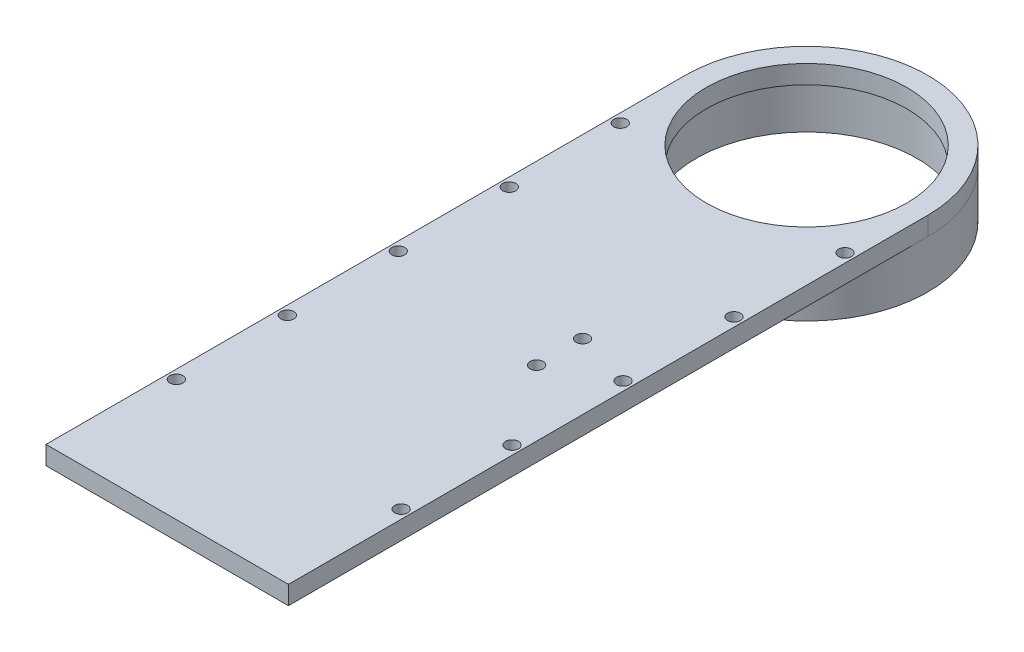
SolidWorks part; units mm, degrees
ref_plane "Front Plane" through (0, 0, 0) normal (0, 0, 1) x (1, 0, 0)
ref_plane "Top Plane" through (0, 0, 0) normal (0, 1, 0) x (1, 0, 0)
ref_plane "Right Plane" through (0, 0, 0) normal (1, 0, 0) x (0, 0, -1)
sketch "Sketch1" plane through (0, 0, 0) normal (0, 1, 0) x (1, 0, 0)
  line L5 (-32.774, -22.3805) -> (-32.774, 177.6195)
  line L6 (32.774, -22.3805) -> (32.774, 177.6195)
  circle A3 centre (0, 177.6195) radius 4.5
  circle A4 centre (0, 67.6378) radius 4.5
  circle A5 centre (15, 89.6378) radius 1.75
  circle A7 centre (-6.7334, 37.1195) radius 1.25
  circle A8 centre (-6.7334, 27.6195) radius 1.25
  circle A14 centre (0, 53.6052) radius 1.75
  circle A15 centre (-14.0327, 67.6378) radius 1.75
  circle A16 centre (0, 81.6705) radius 1.75
  circle A17 centre (14.0327, 67.6378) radius 1.75
  circle A18 centre (0, 67.6378) radius 11.5
  circle A19 centre (0, 67.6378) radius 4.5
  arc A22 (32.774, -22.3805) -> (-32.774, -22.3805) centre (0, -22.3805) cw
  arc A23 (32.774, 177.6195) -> (-32.774, 177.6195) centre (0, 177.6195) ccw
  circle A25 centre (0, -9.3805) radius 2.75
  circle A27 centre (11.2583, -15.8805) radius 2.75
  circle A28 centre (11.2583, -28.8805) radius 2.75
  circle A29 centre (0, -35.3805) radius 2.75
  circle A30 centre (-11.2583, -28.8805) radius 2.75
  circle A31 centre (-11.2583, -15.8805) radius 2.75
  dimension "D1" = 13
  dimension "D2" = 200
  dimension "D3" = 50
  dimension "D4" = 109.9817
  dimension "D5" = 22
  dimension "D8" = 9.5
  dimension "D6" = 15
extrude "Boss-Extrude10" add sketch "Sketch1" against normal blind 5 contours L6 A23 L5 A22 A31 A30 A29 A28 A27 A25 A3 A5 A7 A8 A14 A15 A16 A17 A18 | A18 | A19 region at (-30.0388, 0, -77.6195)
sketch "Sketch2" plane through (0, 0, 0) normal (0, -1, 0) x (1, 0, 0)
  line L30 (28, -177.6198) -> (28, -97.6193)
  line L31 (-28, -4.769) -> (-32.774, -4.769)
  line L35 (-28, -177.6198) -> (-28, -97.62)
  line L46 (-28, -4.769) -> (28, -4.769)
  line L53 (28, -4.769) -> (32.774, -4.769)
  line L54 (-32.774, 22.3805) -> (-32.774, -177.6198)
  line L55 (32.774, 22.3805) -> (32.774, -177.6198)
  line L56 (-28, 22.3805) -> (-28, -97.62)
  line L57 (28, -97.6193) -> (28, 22.3805)
  circle A4 centre (-18, -157.4003) radius 1.75
  circle A5 centre (18.0605, -157.4003) radius 1.75
  circle A6 centre (-18, -97.6199) radius 1.75
  circle A7 centre (18.0032, -97.4003) radius 1.75
  arc A15 (28, -177.6198) -> (-28, -177.6198) centre (0, -177.6198) cw
  arc A26 (32.774, 22.3805) -> (-32.774, 22.3805) centre (0, 22.3805) ccw
  arc A28 (-32.774, -177.6198) -> (32.774, -177.6198) centre (0, -177.6198) ccw
  arc A29 (28, 22.3805) -> (-28, 22.3805) centre (0, 22.3805) ccw
  dimension "D1" = 60
extrude "Boss-Extrude11" add sketch "Sketch1<16>" against normal blind 5 contours A7 | A8 region at (-6.7334, 0, -37.1195) region at (-6.7334, 0, -27.6195)
sketch "Sketch1<16>" plane through (0, 0, 0) normal (0, 1, 0) x (1, 0, 0) same geometry as "Sketch1"
sketch "Sketch3" plane through (0, -5, 0) normal (0, -1, 0) x (1, 0, 0)
  line L2 (-32.774, 22.3805) -> (-32.774, -177.6195) construction
  circle A0 centre (15, -89.6378) radius 1.75
  circle A4 centre (15, -102.0563) radius 1.75
  circle A6 centre (-30.384, -67.6195) radius 1.75
  circle A7 centre (-30.384, -37.6195) radius 1.75
  arc A8 (32.774, 22.3805) -> (-32.774, 22.3805) centre (0, 22.3805) ccw construction
  circle A9 centre (-30.384, -97.6195) radius 1.75
  circle A10 centre (-30.384, -127.6195) radius 1.75
  circle A11 centre (-30.384, -157.6195) radius 1.75
  circle A13 centre (30.384, -157.6195) radius 1.75
  circle A14 centre (30.384, -127.6195) radius 1.75
  circle A15 centre (30.384, -97.6195) radius 1.75
  circle A16 centre (30.384, -67.6195) radius 1.75
  circle A17 centre (30.384, -37.6195) radius 1.75
  dimension "D1" = 60
  dimension "D2" = 2.39
  dimension "D3" = 5
extrude "Cut-Extrude5" cut sketch "Sketch3" against normal blind 17
extrude "Cut-Extrude7" cut sketch "Sketch2" along normal blind 10 contours A29 L57 L53 L55 A26 L54 L31 L56 | L57 A29 L56 L46 region at (28.8881, 0, 8.8057) region at (0, 0, 20.1987)
extrude "Boss-Extrude12" add sketch "Sketch1<18>" against normal blind 5 contours A4 | A17 | A16 | A14 | A15 region at (0, 0, -67.6378) region at (0, 0, -53.6052) region at (-14.0327, 0, -67.6378) region at (0, 0, -81.6705) region at (14.0327, 0, -67.6378)
sketch "Sketch1<18>" plane through (0, 0, 0) normal (0, 1, 0) x (1, 0, 0) same geometry as "Sketch1"
sketch "Sketch5" plane through (0, -5, 0) normal (0, -1, 0) x (1, 0, 0)
  text T0 "<b>       JN V1</b>" font "Century Gothic" height in points 72
sketch "Sketch10" plane through (0, -5, 0) normal (0, -1, 0) x (1, 0, 0)
  circle A0 centre (0, -177.6195) radius 29.85
  circle A1 centre (0, -177.6195) radius 32.768
extrude "Boss-Extrude13" add sketch "Sketch10" along normal blind 13
sketch "Sketch11" plane through (0, -5, 0) normal (0, -1, 0) x (1, 0, 0)
  circle A0 centre (0, -177.6195) radius 27.095
extrude "Cut-Extrude8" cut sketch "Sketch11" against normal blind 13
extrude "Boss-Extrude14" add sketch "Sketch5" along normal blind 3
sketch "Sketch13" plane through (0, -5, 0) normal (0, -1, 0) x (1, 0, 0)
  line L1 (-5.999, -121.1011) -> (6.001, -121.1011)
  line L2 (-5.999, -121.1011) -> (-5.999, -125.1011)
  line L3 (-5.999, -125.1011) -> (6.001, -125.1011)
  line L4 (6.001, -121.1011) -> (6.001, -125.1011)
  line L5 (-5.999, -121.1011) -> (6.001, -125.1011) construction
  line L6 (-5.999, -125.1011) -> (6.001, -121.1011) construction
  line L8 (-32.774, -4.769) -> (-32.774, -177.6195) construction
  point P0 (0.001, -123.1011)
  dimension "D1" = 12
  dimension "D2" = 26.775
extrude "Boss-Extrude15" add sketch "Sketch13" along normal blind 25
sketch "Sketch14" plane through (0, 0, -125.1011) normal (0, 0, -1) x (-1, 0, 0)
  line L2 (5.999, -30) -> (-6.001, -30) construction
  circle A0 centre (0, -22.5) radius 1.25
  circle A1 centre (0, -13) radius 1.25
  dimension "D1" = 7.5
  dimension "D2" = 9.5
extrude "Cut-Extrude9" cut sketch "Sketch14" against normal blind 25
fillet "Fillet1" radius 2.5 4 edges at (6.001, -30, -123.1011) (-5.999, -30, -123.1011) (-5.999, -5, -123.1011) (6.001, -5, -123.1011)
